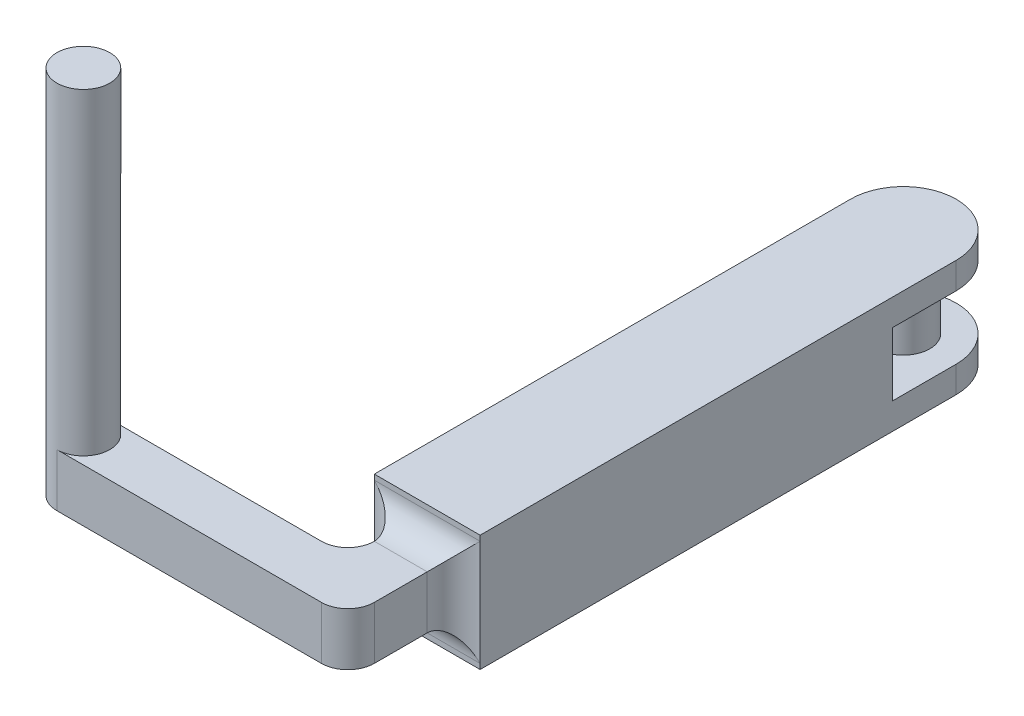
SolidWorks part; units mm, degrees
ref_plane "Front Plane" through (0, 0, 0) normal (0, 0, 1) x (1, 0, 0)
ref_plane "Top Plane" through (0, 0, 0) normal (0, 1, 0) x (1, 0, 0)
ref_plane "Right Plane" through (0, 0, 0) normal (1, 0, 0) x (0, 0, -1)
sketch "Sketch1" plane through (0, 0, 0) normal (0, 1, 0) x (1, 0, 0)
  circle A0 centre (0, 0) radius 3.175
  dimension "D1" = 6.35
extrude "Boss-Extrude1" add sketch "Sketch1" against normal blind 38.1
sketch "Sketch2" plane through (0, 0, 0) normal (0, 1, 0) x (1, 0, 0)
  line L0 (0, 0) -> (0, 3.175) construction
  line L1 (34.925, 3.175) -> (-3.175, 3.175) construction
  line L2 (34.925, 3.175) -> (34.925, -3.175) construction
  line L3 (34.925, -3.175) -> (-3.175, -3.175)
  line L4 (-3.175, 3.175) -> (-3.175, -3.175)
  line L5 (34.925, 3.175) -> (-3.175, -3.175) construction
  line L6 (34.925, -3.175) -> (-3.175, 3.175) construction
  line L7 (0, 0) -> (-3.175, 0) construction
  line L8 (-3.175, 3.175) -> (28.575, 3.175)
  line L9 (28.575, 3.175) -> (28.575, 60.325)
  line L10 (28.575, 60.325) -> (34.925, 60.325)
  line L11 (34.925, 60.325) -> (34.925, -3.175)
  point P0 (15.875, 0)
  dimension "D1" = 6.35
  dimension "D2" = 38.1
  dimension "D3" = 6.35
  dimension "D4" = 63.5
extrude "Boss-Extrude2" add sketch "Sketch2" along normal blind 6.35
fillet "Fillet1" radius 3.175 4 edges at (28.575, 3.175, -3.175) (34.925, 3.175, 3.175) (-3.175, 3.175, -3.175) (-3.175, 3.175, 3.175)
sketch "Sketch3" plane through (0, 6.35, 0) normal (0, 1, 0) x (1, 0, 0)
  line L0 (25.4, 41.275) -> (31.75, 41.275) construction
  line L1 (25.4, 9.525) -> (38.1, 9.525)
  line L2 (25.4, 9.525) -> (25.4, 73.025)
  line L3 (25.4, 73.025) -> (38.1, 73.025)
  line L4 (38.1, 9.525) -> (38.1, 73.025)
  line L5 (31.75, 41.275) -> (31.75, 73.025) construction
  line L6 (34.925, 60.325) -> (28.575, 60.325) construction
  line L7 (0, -3.175) -> (31.75, -3.175) construction
  point P9 (31.75, 60.325)
  dimension "D1" = 12.7
  dimension "D2" = 12.7
  dimension "D3" = 63.5
extrude "Boss-Extrude3" add sketch "Sketch3" against normal blind 10.16 and the other way blind 3.81
fillet "Fillet2" radius 3.175 4 edges at (28.575, 3.175, -9.525) (31.75, 0, -9.525) (34.925, 3.175, -9.525) (31.75, 6.35, -9.525)
fillet "Fillet3" radius 6.35 2 edges at (25.4, 3.175, -73.025) (38.1, 3.175, -73.025)
sketch "Sketch4" plane through (38.1, 0, 0) normal (1, 0, 0) x (0, 0, -1)
  line L0 (66.675, -3.81) -> (66.675, 10.16) construction
  line L1 (59.055, -0.635) -> (74.295, -0.635)
  line L2 (59.055, -0.635) -> (59.055, 6.985)
  line L3 (59.055, 6.985) -> (74.295, 6.985)
  line L4 (74.295, -0.635) -> (74.295, 6.985)
  line L5 (59.055, -0.635) -> (74.295, 6.985) construction
  line L6 (59.055, 6.985) -> (74.295, -0.635) construction
  line L7 (73.025, 10.16) -> (73.025, -3.81) construction
  point P0 (66.675, 3.175)
  dimension "D1" = 7.62
  dimension "D2" = 13.97
extrude "Cut-Extrude1" cut sketch "Sketch4" against normal up to next
sketch "Sketch5" plane through (0, -0.635, 0) normal (0, 1, 0) x (1, 0, 0)
  circle A0 centre (31.75, 66.675) radius 3.175
  arc A1 (31.75, 73.025) -> (25.4, 66.675) centre (31.75, 66.675) ccw construction
  dimension "D1" = 6.35
extrude "Boss-Extrude4" add sketch "Sketch5" along normal blind 10.16
sketch "Sketch6" plane through (0, 6.35, 0) normal (0, 1, 0) x (1, 0, 0)
  circle A0 centre (0, 0) radius 3.175
  arc A1 (0, 3.175) -> (-3.175, 0) centre (0, 0) ccw construction
extrude "Boss-Extrude5" add sketch "Sketch6" along normal blind 38.1
sketch "Sketch7" plane through (0, 0, 0) normal (0, -1, 0) x (1, 0, 0)
  circle A0 centre (0, 0) radius 3.175
  circle A1 centre (0, 0) radius 3.175 construction
extrude "Cut-Extrude2" cut sketch "Sketch7" along normal blind 38.1 body kept at (25.4, 10.16, -66.6751)
